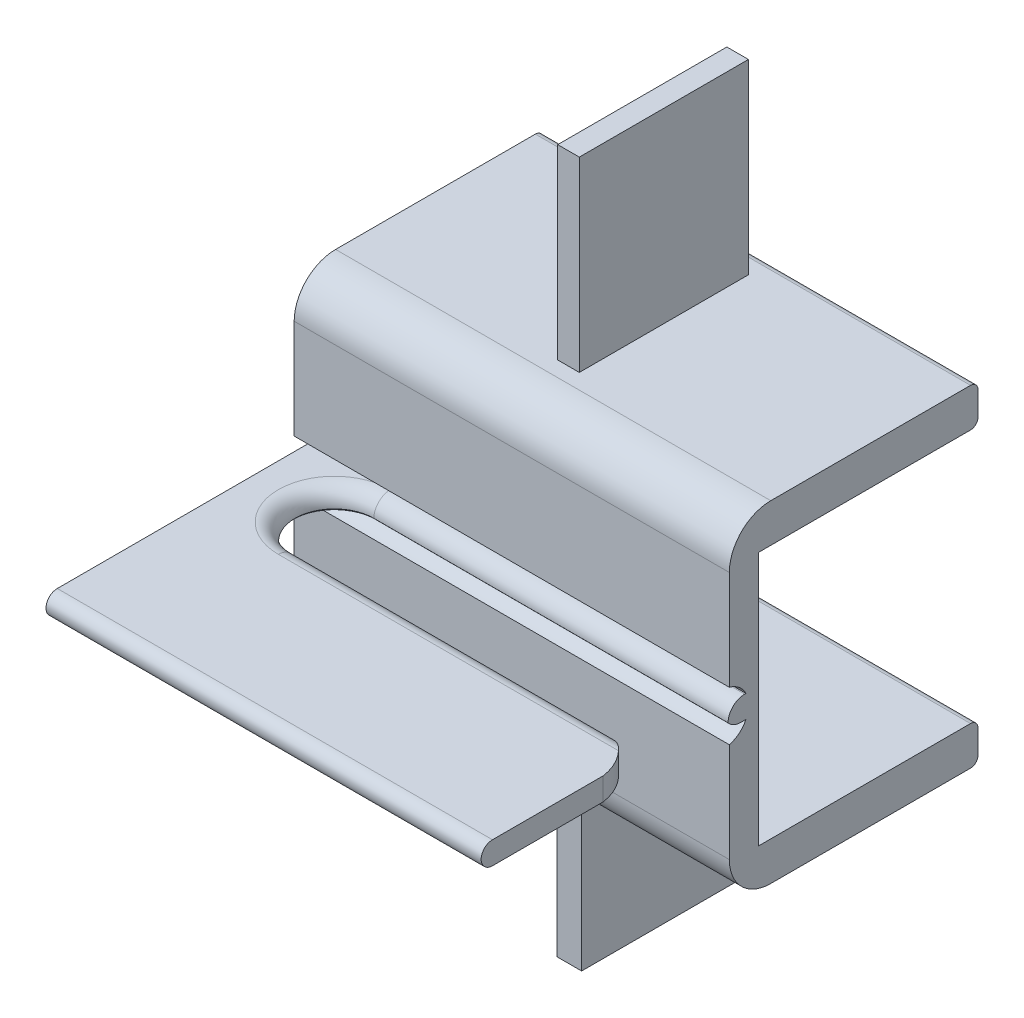
SolidWorks part; units mm, degrees
ref_plane "Plano frontal" through (0, 0, 0) normal (0, 0, 1) x (1, 0, 0)
ref_plane "Plano superior" through (0, 0, 0) normal (0, 1, 0) x (1, 0, 0)
ref_plane "Plano direito" through (0, 0, 0) normal (1, 0, 0) x (0, 0, -1)
sketch "Esboço1" plane through (0, 0, 0) normal (1, 0, 0) x (0, 0, -1)
  line L0 (1.15, 1.5333) -> (1.41, 1.5333)
  line L1 (-1, -2) -> (1.41, -2)
  line L2 (-1.5, -1.5) -> (-1.5, -0.3)
  line L3 (-1, 2) -> (1.41, 2)
  line L4 (1.5, -1.91) -> (1.5, -1.6233)
  line L6 (-4.3577, 0.1362) -> (-1.2998, 0.1362)
  line L7 (-1.15, -1.5333) -> (1.15, -1.5333)
  line L8 (-1.15, -1.5333) -> (-1.15, 1.5333)
  line L9 (-1.15, 1.5333) -> (1.15, 1.5333)
  line L10 (-1.5, 0.3) -> (-1.5, 1.5)
  line L11 (-4.3577, -0.1362) -> (-1.2998, -0.1362)
  line L13 (1.15, -1.5333) -> (1.41, -1.5333)
  line L14 (1.5, 1.6233) -> (1.5, 1.91)
  arc A0 (-1.5, 0.3) -> (-1.2998, 0.1362) centre (-1.5783, 0) cw
  arc A1 (-4.3577, 0.1362) -> (-4.3577, -0.1362) centre (-4.3577, 0) ccw
  arc A2 (-1.2998, -0.1362) -> (-1.5, -0.3) centre (-1.5783, 0) cw
  arc A3 (1.5, -1.91) -> (1.41, -2) centre (1.41, -1.91) cw
  arc A4 (1.5, -1.6233) -> (1.41, -1.5333) centre (1.41, -1.6233) ccw
  arc A5 (1.5, 1.6233) -> (1.41, 1.5333) centre (1.41, 1.6233) cw
  arc A6 (1.5, 1.91) -> (1.41, 2) centre (1.41, 1.91) ccw
  arc A7 (-1, -2) -> (-1.5, -1.5) centre (-1, -1.5) cw
  arc A8 (-1.5, 1.5) -> (-1, 2) centre (-1, 1.5) cw
  point P0 (0, 0)
  point P6 (0, 0)
  point P18 (-1.5783, 0)
  point P28 (1.5, 1.5333)
  point P31 (1.5, 2)
  point P34 (-1.5, -2)
  point P37 (-1.5, 2)
  dimension "D4" = 0.09
  dimension "D5" = 0.5
  dimension "D1" = 4
  dimension "D2" = 3
  dimension "D3" = 0.35
extrude "Ressalto-extrusão1" add sketch "Esboço1" along normal blind 5.25
sketch "Esboço3" plane through (0, 0.1362, 0) normal (0, 1, 0) x (1, 0, 0)
  line L1 (0.9764, -1.5149) -> (7.8941, -1.5149)
  line L2 (0.9764, -2.4672) -> (7.8941, -2.4672)
  arc A0 (0.9764, -1.5149) -> (0.9764, -2.4672) centre (0.9764, -1.9911) ccw
  arc A1 (7.8941, -2.4672) -> (7.8941, -1.5149) centre (7.8941, -1.9911) ccw
  point P2 (4.4353, -1.9911)
extrude "Corte-extrusão1" cut sketch "Esboço3" against normal blind 5.25
sketch "Esboço4" plane through (0, 0.1362, 0) normal (0, 1, 0) x (1, 0, 0)
  line L0 (0.9764, -2.4672) -> (5.25, -2.4672) construction
  line L1 (5.25, -2.4672) -> (5.25, -4.3577) construction
  line L2 (4.6958, -2.4672) -> (4.8845, -1.9372)
  line L3 (4.8845, -1.9372) -> (6.0074, -2.0989)
  line L4 (6.0074, -2.0989) -> (6.3758, -3.2668)
  line L5 (6.3758, -3.2668) -> (5.25, -3.2039)
  arc A0 (4.6958, -2.4672) -> (5.25, -3.2039) centre (4.6046, -3.1127) cw
extrude "Corte-extrusão2" cut sketch "Esboço4" against normal blind 5.25
fillet "Filete1" radius 0.2 3 edges at (2.8361, 0.1362, 2.4672) (0.5003, 0.1362, 1.9911) (3.1132, 0.1362, 1.5149)
fillet "Filete2" radius 0.2 3 edges at (2.8361, -0.1362, 2.4672) (0.5003, -0.1362, 1.9911) (3.1132, -0.1362, 1.5149)
sketch "Esboço5" plane through (0, 2, 0) normal (0, 1, 0) x (1, 0, 0)
  line L4 (2.4947, -0.8152) -> (2.7553, -0.8152)
  line L5 (2.4947, -0.8152) -> (2.4947, 1.2252)
  line L6 (2.4947, 1.2252) -> (2.7553, 1.2252)
  line L7 (2.7553, -0.8152) -> (2.7553, 1.2252)
  point P6 (2.625, 0.205)
extrude "Ressalto-extrusão2" add sketch "Esboço5" along normal blind 2.25
sketch "Esboço6" plane through (0, -2, 0) normal (0, -1, 0) x (1, 0, 0)
  line L4 (2.4768, -1.2152) -> (2.7732, -1.2152)
  line L5 (2.4768, -1.2152) -> (2.4768, 0.8052)
  line L6 (2.4768, 0.8052) -> (2.7732, 0.8052)
  line L7 (2.7732, -1.2152) -> (2.7732, 0.8052)
  point P6 (2.625, -0.205)
extrude "Ressalto-extrusão3" add sketch "Esboço6" along normal blind 2.25
